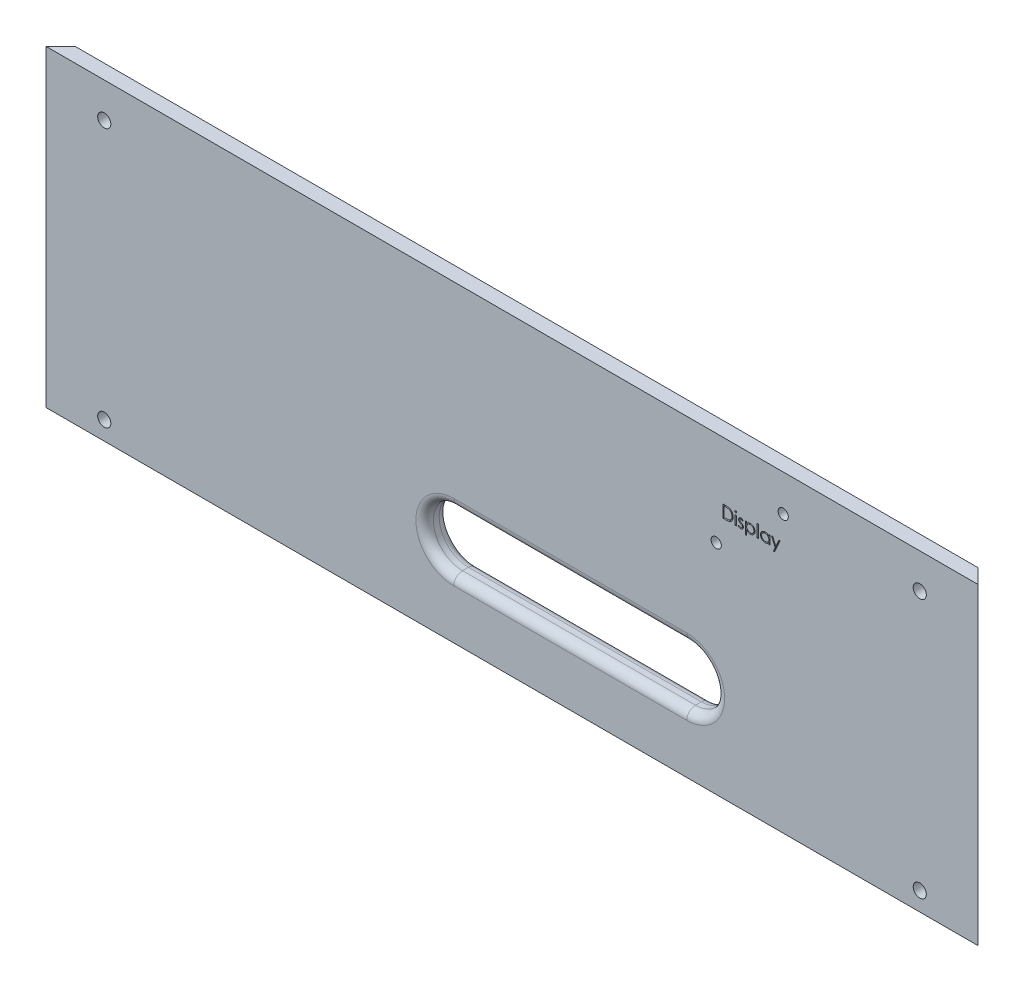
SolidWorks part; units mm, degrees
ref_plane "Front Plane" through (0, 0, 0) normal (0, 0, 1) x (1, 0, 0)
ref_plane "Top Plane" through (0, 0, 0) normal (0, 1, 0) x (1, 0, 0)
ref_plane "Right Plane" through (0, 0, 0) normal (1, 0, 0) x (0, 0, -1)
sketch "Sketch1" plane through (0, 0, 0) normal (0, 0, 1) x (1, 0, 0)
  line L0 (160, 110) -> (160, -37.3998) construction
  line L1 (0, 0) -> (320, 0)
  line L2 (0, 0) -> (0, 110)
  line L3 (0, 110) -> (320, 110)
  line L4 (320, 0) -> (320, 110)
  line L5 (0, 55) -> (320, 55) construction
  circle A0 centre (20, 9) radius 2.25
  circle A1 centre (300, 9) radius 2.25
  circle A4 centre (20, 98) radius 2.25
  circle A5 centre (300, 98) radius 2.25
  dimension "D3" = 20
  dimension "D5" = 4.5
  dimension "D1" = 110
  dimension "D2" = 320
  dimension "D4" = 9
  dimension "D6" = 2
  dimension "D7" = 12
extrude "Boss-Extrude1" add sketch "Sketch1" against normal blind 5
sketch "Sketch2" plane through (0, 0, -5) normal (0, 0, -1) x (-1, 0, 0)
  line L0 (0, 0) -> (-320, 0) construction
  line L1 (0, 0) -> (-320, 0) construction
  line L2 (0, 5) -> (-320, 5)
  line L3 (-320, 5) -> (-320, 110)
  line L4 (-320, 110) -> (0, 110)
  line L5 (0, 110) -> (0, 5)
  circle A1 centre (-20, 9) radius 2.25 construction
  circle A2 centre (-300, 9) radius 2.25 construction
  circle A5 centre (-20, 9) radius 2.25
  circle A6 centre (-300, 9) radius 2.25
  circle A8 centre (-20, 98) radius 2.25 construction
  circle A9 centre (-300, 98) radius 2.25 construction
  circle A10 centre (-20, 98) radius 2.25
  circle A11 centre (-300, 98) radius 2.25
  dimension "D1" = 5
extrude "Boss-Extrude2" add sketch "Sketch2" along normal blind 3
chamfer "Chamfer1" distance 8 angle 45 3 edges at (320, 57.5, -8) (0, 57.5, -8) (160, 110, -8)
chamfer "Chamfer3" distance 3 angle 45 1 edges at (160, 110, -8)
sketch "Sketch3" plane through (160, 0, -160) normal (0.7071, 0, -0.7071) x (-0.7071, 0, -0.7071)
  line L0 (-226.2742, 0) -> (-226.2742, 2.6)
  line L1 (-226.2742, 0) -> (-226.2742, 110) construction
  line L2 (-226.2742, 2.6) -> (-219.2031, 2.6)
  line L4 (-219.2031, 2.6) -> (-219.2031, 0)
  line L5 (-219.2031, 0) -> (-226.2742, 0)
  line L6 (-214.9605, 5) -> (-219.2031, 5) construction
  dimension "D1" = 2.4
extrude "Cut-Extrude1" cut sketch "Sketch3" along direction (1, 0, 0) on the side against the normal through all
sketch "Sketch4" plane through (0, 0, 0) normal (0, 0, 1) x (1, 0, 0)
  line L0 (320, 110) -> (0, 110) construction
  circle A0 centre (253.1162, 97.5) radius 1.75
  circle A1 centre (230.1162, 77.5) radius 1.75
  dimension "D1" = 3.5
  dimension "D2" = 3.5
  dimension "D3" = 12.5
  dimension "D4" = 23
  dimension "D5" = 20
extrude "Cut-Extrude2" cut sketch "Sketch4" against normal through all
sketch "Sketch5" plane through (0, 0, 0) normal (0, 0, 1) x (1, 0, 0)
  line L0 (231.9046, 85.9202) -> (252.0147, 85.9202) construction
  text T0 "Display" font "Century Gothic" height in points 16
extrude "Cut-Extrude3" cut sketch "Sketch5" against normal blind 0.5
sketch "Sketch6" plane through (0, 0, 0) normal (0, 0, 1) x (1, 0, 0)
  line L0 (140, 32.6) -> (220, 32.6) construction
  line L1 (140, 42.6) -> (220, 42.6)
  line L2 (140, 22.6) -> (220, 22.6)
  line L4 (0, 2.6) -> (320, 2.6) construction
  line L5 (320, 2.6) -> (320, 110) construction
  arc A0 (140, 42.6) -> (140, 22.6) centre (140, 32.6) ccw
  arc A1 (220, 22.6) -> (220, 42.6) centre (220, 32.6) ccw
  point P2 (180, 32.6)
  dimension "D1" = 20
  dimension "D2" = 20
  dimension "D3" = 100
  dimension "D4" = 80
extrude "Cut-Extrude4" cut sketch "Sketch6" against normal up to next
fillet "Fillet1" radius 3 8 edges at (130, 32.6, 0) (180, 42.6, 0) (230, 32.6, 0) (180, 22.6, 0) (230, 32.6, -8) (180, 42.6, -8) (130, 32.6, -8) (180, 22.6, -8)
